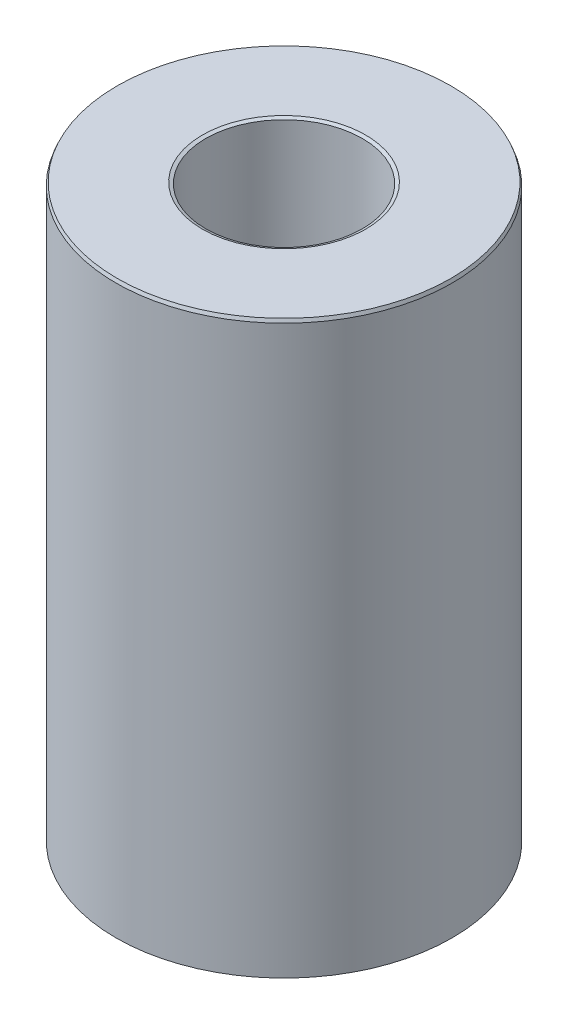
SolidWorks part; units mm, degrees
ref_plane "Front Plane" through (0, 0, 0) normal (0, 0, 1) x (1, 0, 0)
ref_plane "Top Plane" through (0, 0, 0) normal (0, 1, 0) x (1, 0, 0)
ref_plane "Right Plane" through (0, 0, 0) normal (1, 0, 0) x (0, 0, -1)
sketch "Sketch1" plane through (0, 0, 0) normal (0, 1, 0) x (1, 0, 0)
  circle A0 centre (0, 0) radius 55
  dimension "SLEEVE_OD" = 110
extrude "Boss-Extrude1" add sketch "Sketch1" along normal blind 187.0213
sketch "Sketch2" plane through (0, 0, 0) normal (0, 1, 0) x (1, 0, 0)
  circle A0 centre (0, 0) radius 25.6113
  dimension "BORE_D" = 51.2226
extrude "Cut-Extrude1" cut sketch "Sketch2" along normal through all
chamfer "Chamfer1" distance 1.0874 angle 21.549 4 edges at (0, 187.0213, 25.6113) (0, 0, 25.6113) (0, 0, 55) (0, 187.0213, 55) first distance on face at (0, 187.0213, 25.6113) first distance on face at (0, 0, 25.6113) first distance on face at (0, 187.0213, 55)
